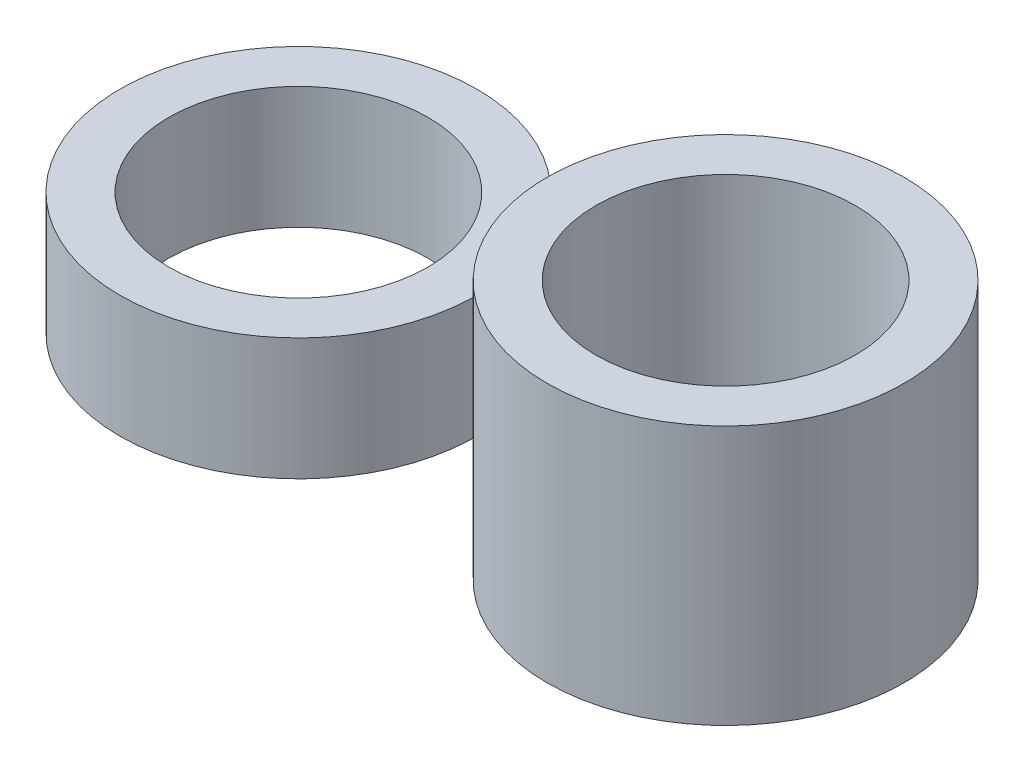
SolidWorks part; units mm, degrees
ref_plane "Front Plane" through (0, 0, 0) normal (0, 0, 1) x (1, 0, 0)
ref_plane "Top Plane" through (0, 0, 0) normal (0, 1, 0) x (1, 0, 0)
ref_plane "Right Plane" through (0, 0, 0) normal (1, 0, 0) x (0, 0, -1)
sketch "Sketch1" plane through (0, 0, 0) normal (0, 1, 0) x (1, 0, 0)
  circle A0 centre (0, 0) radius 4.25
  circle A1 centre (0, 0) radius 5.85
  dimension "D1" = 8.5
  dimension "D2" = 1.6
extrude "Boss-Extrude1" add sketch "Sketch1" along normal blind 8.5
sketch "Sketch2" plane through (0, 0, 0) normal (0, 1, 0) x (1, 0, 0)
  circle A0 centre (-14, 0) radius 4.25
  circle A1 centre (0, 0) radius 4.25 construction
  circle A2 centre (-14, 0) radius 5.85
  circle A3 centre (0, 0) radius 5.85 construction
  point P8 (0, 0)
  dimension "D1" = 14
extrude "Boss-Extrude2" add sketch "Sketch2" along normal blind 4 separate body
